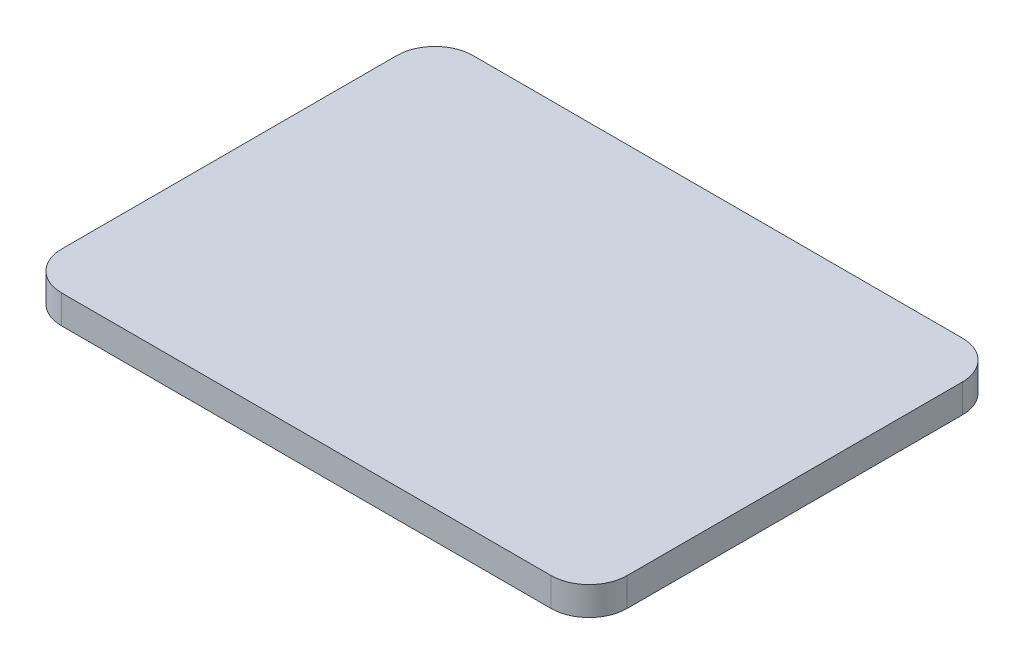
SolidWorks part; units mm, degrees
ref_plane "Спереди" through (0, 0, 0) normal (0, 0, 1) x (1, 0, 0)
ref_plane "Сверху" through (0, 0, 0) normal (0, 1, 0) x (1, 0, 0)
ref_plane "Справа" through (0, 0, 0) normal (1, 0, 0) x (0, 0, -1)
sketch "Эскиз1" plane through (0, 0, 0) normal (0, 1, 0) x (1, 0, 0)
  line L1 (-128.5, 108) -> (128.5, 108)
  line L2 (-148.5, 88) -> (-148.5, -88)
  line L3 (-128.5, -108) -> (128.5, -108)
  line L4 (148.5, 88) -> (148.5, -88)
  line L5 (-148.5, 108) -> (148.5, -108) construction
  line L6 (-148.5, -108) -> (148.5, 108) construction
  arc A0 (-128.5, 108) -> (-148.5, 88) centre (-128.5, 88) ccw
  arc A1 (-148.5, -88) -> (-128.5, -108) centre (-128.5, -88) ccw
  arc A2 (128.5, -108) -> (148.5, -88) centre (128.5, -88) ccw
  arc A3 (128.5, 108) -> (148.5, 88) centre (128.5, 88) cw
  point P0 (0, 0)
  point P9 (0, 0)
  point P10 (0, 0)
  point P11 (0, 0)
  dimension "D1" = 20
  dimension "D2" = 20
extrude "Бобышка-Вытянуть1" add sketch "Эскиз1" along normal blind 15
